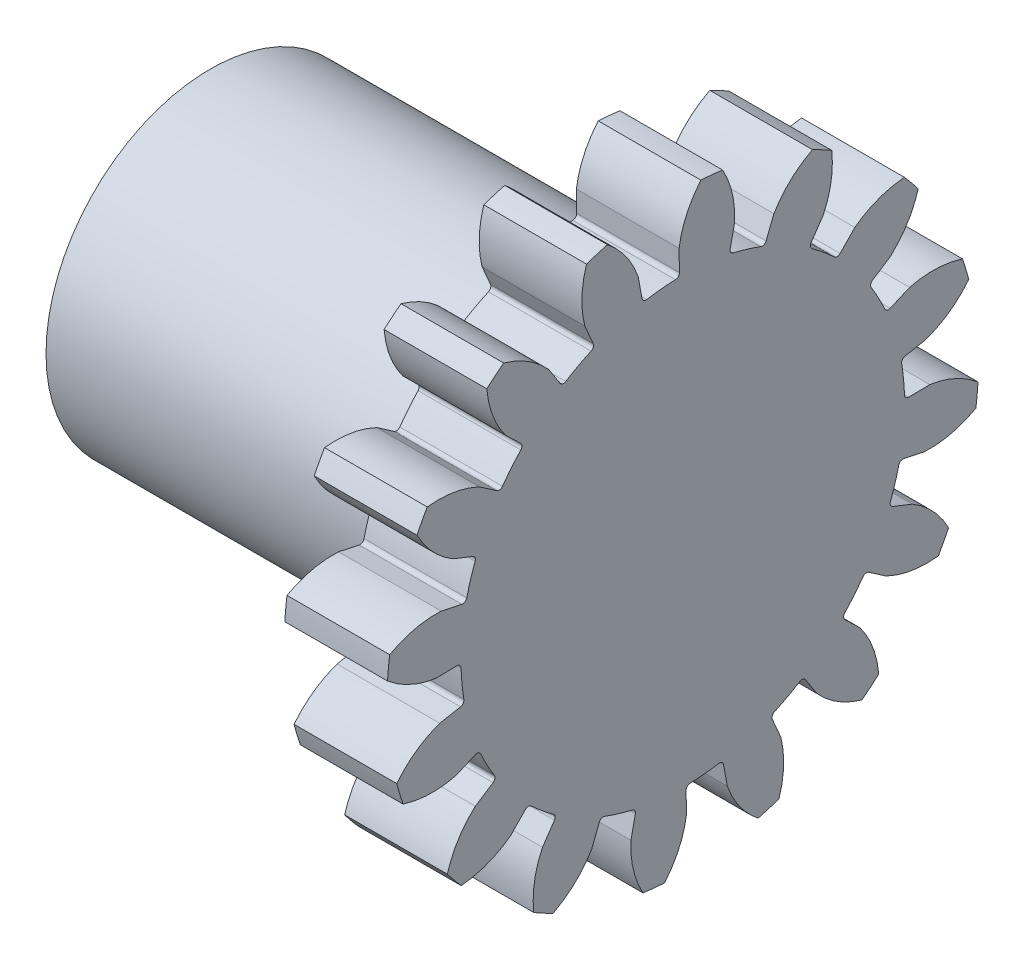
SolidWorks part; units mm, degrees
ref_plane "Спереди" through (0, 0, 0) normal (0, 0, 1) x (1, 0, 0)
ref_plane "Сверху" through (0, 0, 0) normal (0, 1, 0) x (1, 0, 0)
ref_plane "Справа" through (0, 0, 0) normal (1, 0, 0) x (0, 0, -1)
sketch "Эскиз2" plane through (0, 0, 0) normal (1, 0, 0) x (0, 0, -1)
  circle A0 centre (0, 0) radius 5.4
  dimension "D1" = 10.8
extrude "Бобышка-Вытянуть2" add sketch "Эскиз2" along normal blind 2.5
sketch "Эскиз5" plane through (0, 0, 0) normal (-1, 0, 0) x (0, 0, 1)
  circle A0 centre (0, 0) radius 4
  dimension "D1" = 8
extrude "Бобышка-Вытянуть4" add sketch "Эскиз5" along normal blind 9
hole_wizard "Отверстие обработанное метчиком M31" positions "Эскиз6" profile "Эскиз7" tap size "M3" standard "ISO"
sketch "Эскиз6" plane through (-9, 0, 0) normal (-1, 0, 0) x (0, 0, 1)
  point P0 (0, 0)
sketch "Эскиз7" plane through (-9, 0, 0) normal (0, 1, 0) x (0, 0, 1)
  line L0 (0, 0) -> (0, 9.2511)
  line L1 (0, 9.2511) -> (1.25, 8.5)
  line L2 (1.25, 8.5) -> (1.25, 1.25)
  line L3 (1.25, 1.25) -> (2.5, 0)
  line L5 (2.5, 0) -> (0, 0)
  line L6 (-1.25, 1.25) -> (-2.5, 0) construction
  line L10 (0, 9.2511) -> (-1.25, 8.5) construction
  line L11 (0, -6.35) -> (0, 107.95) construction
  dimension "Диаметр сверла" = 2.5
  dimension "Глубина сверла" = 8.5
  dimension "Диаметр передней зенковки" = 5
  dimension "Угол передней зенковки" = 90
  dimension "Угол заточки сверла" = 118
cosmetic thread "Отверстие резьбы1" parameters "D1"=0, "D2"=3.5
ref_plane "Плоскость2" through (1.25, 0, 0) normal (1, 0, 0) x (0, 0, -1)
sketch "Эскиз9" plane through (1.25, 0, 0) normal (1, 0, 0) x (0, 0, -1)
  line L0 (0, 0) -> (0, 6.4) construction
  line L1 (0, 6.4) -> (1.2306, 6.4) construction
  line L2 (0, 6.4) -> (2.0569, 5.6513) construction
  line L3 (0.4403, 7.1865) -> (3.6077, 4.8118) construction
  line L4 (0, 0) -> (-0.0896, 6.0134) construction
  line L5 (-0.0896, 6.0134) -> (-0.0805, 5.3994)
  line L6 (0, 0) -> (0.7057, 7.1653) construction
  line L7 (1.2611, 5.8803) -> (1.1323, 5.28)
  arc A0 (0.9702, 7.1343) -> (0.4403, 7.1865) centre (0, 0) ccw
  circle A1 centre (0, 0) radius 6.4 construction
  circle A2 centre (0, 0) radius 5.4 construction
  arc A3 (1.1323, 5.28) -> (-0.0805, 5.3994) centre (0, 0) ccw
  circle A4 centre (0, 0) radius 6.014 construction
  spline S0 degree 2 poles (-0.0896, 6.0134) (0.0048, 6.6659) (0.4403, 7.1865) knots 0 0 0 1 1 1
  spline S1 degree 2 poles (1.2611, 5.8803) (1.2957, 6.5388) (0.9702, 7.1343) knots 0 0 0 1 1 1
  point P11 (-0.0896, 6.0134)
  dimension "D1" = 12.8
  dimension "D2" = 14.4
  dimension "D3" = 20
  dimension "D4" = 2.1889
  dimension "D5" = 3.9587
  dimension "D8" = 5.625
  dimension "D6" = 1.7698
  dimension "D7" = 2.1889
extrude "Бобышка-Вытянуть5" add sketch "Эскиз9" along normal up to surface and the other way up to surface up to face at (2.5, 0, -5.4) other way up to face at (0, 0, 4)
fillet "Скругление4" radius 0.1 2 edges at (1.25, 5.3994, 0.0805) (1.25, 5.28, -1.1323)
pattern_circular "Круговой массив1" count 16 over 360 about axis through (2.5, 0, 0) along (-1, 0, 0) of "Бобышка-Вытянуть5", "Скругление4"
sketch "Эскиз11" plane through (0, 0, 0) normal (0, 0, 1) x (1, 0, 0)
  line L0 (0, 4) -> (0, 3.7)
  line L1 (0, 3.7) -> (-0.5, 3.7)
  line L2 (-0.5, 3.7) -> (-0.8, 4)
  line L3 (0, 4) -> (-9, 4) construction
  line L4 (-0.8, 4) -> (0, 4)
  dimension "D1" = 0.3
  dimension "D2" = 0.8
  dimension "D3" = 45
revolve "Вырез-Повернуть3" cut sketch "Эскиз11" angle 360 about axis through (-9, 0, 0) along (1, 0, 0)
fillet "Скругление5" radius 0.2 2 edges at (-0.5, 0, 3.7) (0, 0, 3.7)
equation "\"Модуль\"= 0.8мм"
equation "\"Число2\"= 16"
equation "\"D1@Эскиз2\"= \"Модуль\" * (\"Число2\" - 2.5)"
equation "\"D1@Эскиз9\"= \"Модуль\" * \"Число2\""
equation "\"D2@Эскиз9\"= \"Модуль\" * (\"Число2\" + 2)"
equation "\"D6@Эскиз9\"= \"D5@Эскиз9\" - \"D4@Эскиз9\""
equation "\"D7@Эскиз9\"= \"D4@Эскиз9\""
equation "\"D8@Эскиз9\"= 90 / \"Число2\""
equation "\"D1@Круговой массив1\"= \"Число2\""
